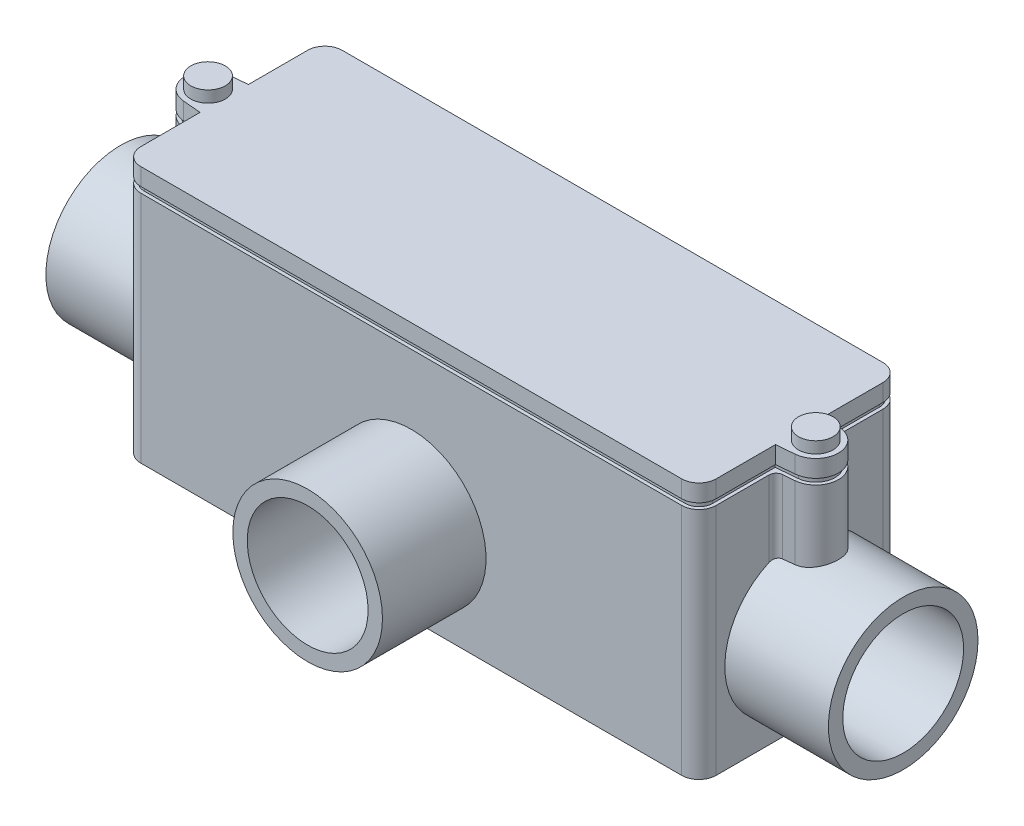
SolidWorks part; units mm, degrees
material "PVC Rigid"
ref_plane "Front" through (0, 0, 0) normal (0, 0, 1) x (1, 0, 0)
ref_plane "Top" through (0, 0, 0) normal (0, 1, 0) x (1, 0, 0)
ref_plane "Right" through (0, 0, 0) normal (1, 0, 0) x (0, 0, -1)
sketch "Sketch2" plane through (0, 0, 0) normal (0, 1, 0) x (1, 0, 0)
  line L0 (63.5, -22.225) -> (-63.5, 22.225) construction
  line L1 (-63.5, 22.225) -> (63.5, 22.225)
  line L2 (-63.5, 22.225) -> (-63.5, -22.225)
  line L3 (-63.5, -22.225) -> (63.5, -22.225)
  line L4 (63.5, 22.225) -> (63.5, -22.225)
  dimension "BoxLength" = 127
  dimension "BoxWidth" = 44.45
extrude "Base-Extrude" add sketch "Sketch2" along normal blind 51.6128
fillet "Fillet1" radius 3.81 4 edges at (-63.5, 25.8064, 22.225) (63.5, 25.8064, 22.225) (63.5, 25.8064, -22.225) (-63.5, 25.8064, -22.225)
shell "Shell1" thickness 3.556 removed face at (0, 51.6128, 0)
ref_plane "Plane1" through (0, -15, 0) normal (0, -1, 0) x (1, 0, 0)
sketch "Sketch1" plane through (63.5, 0, 0) normal (1, 0, 0) x (0, 0, -1)
  line L0 (0, 0) -> (0, 56.0378) construction
  line L2 (-18.415, 0) -> (18.415, 0) construction
  line L3 (-18.415, 0) -> (18.415, 0) construction
  circle A0 centre (0, 19.812) radius 16.51
  point P7 (0, 0)
  dimension "ConduitHubDia" = 33.02
  dimension "D2" = 3.302
extrude "ConduitBoss-Extrude1" add sketch "Sketch1" along normal blind 22.86
sketch "Sketch5" plane through (0, 51.6128, 0) normal (0, 1, 0) x (-1, 0, 0)
  line L0 (0, 0) -> (-73.6061, 0) construction
  line L1 (-63.5, -5.334) -> (-63.5, 5.334)
  line L2 (-63.5, 5.334) -> (-67.5078, 4.9807)
  line L3 (-63.5, -5.334) -> (-67.5078, -4.9807)
  line L4 (-63.5, 18.415) -> (-63.5, -18.415) construction
  line L5 (0, 0) -> (0, -39.7001) construction
  line L7 (63.5, 5.334) -> (67.5078, 4.9807)
  line L8 (63.5, -5.334) -> (67.5078, -4.9807)
  line L9 (63.5, -5.334) -> (63.5, 5.334)
  arc A0 (-67.5078, 4.9807) -> (-67.5078, -4.9807) centre (-67.0687, 0) ccw
  arc A1 (67.5078, 4.9807) -> (67.5078, -4.9807) centre (67.0687, 0) cw
  point P6 (-63.5, 0)
  dimension "D1" = 5
  dimension "D2" = 10.668
  dimension "L2-holeTOhole" = 134.1374
extrude "CoverScrewBoss-Extrude6" add sketch "Sketch5" against normal blind 20
sketch "Sketch18" plane through (0, 0, 22.225) normal (0, 0, 1) x (1, 0, 0)
  line L0 (0, 0) -> (0, 47.1321) construction
  line L1 (-59.69, 0) -> (59.69, 0) construction
  circle A0 centre (0, 19.812) radius 16.51
  dimension "BossOD" = 33.02
  dimension "BossOffsetoffBottom" = 3.302
extrude "SideConduitBoss-Extrude2" add sketch "Sketch18" along normal blind 22.86
sketch "Sketch10" plane through (86.36, 0, 0) normal (1, 0, 0) x (0, 0, -1)
  circle A0 centre (0, 19.812) radius 13.335
  circle A1 centre (0, 19.812) radius 16.51 construction
  dimension "ConduitSocketDia" = 26.67
extrude "ConduitSocket-Cut-Extrude4" cut sketch "Sketch10" against normal blind 19.8374
sketch "Sketch16" plane through (66.5226, 0, 0) normal (1, 0, 0) x (0, 1, 0)
  circle A0 centre (19.812, 0) radius 10.795
  circle A1 centre (19.812, 0) radius 16.51 construction
  dimension "ThruDIA" = 21.59
extrude "ThruDia-Cut-Extrude7" cut sketch "Sketch16" against normal up to surface (6.5786 mm away) up to face at (59.944, 27.5844, 0)
mirror "Mirror1" about plane through (0, 0, 0) normal (1, 0, 0) of "ConduitBoss-Extrude1", "ConduitSocket-Cut-Extrude4", "ThruDia-Cut-Extrude7"
sketch "Sketch19" plane through (0, 0, 45.085) normal (0, 0, 1) x (1, 0, 0)
  circle A0 centre (0, 19.812) radius 13.335
  circle A1 centre (0, 19.812) radius 16.51 construction
  dimension "CondSocketDia" = 26.67
extrude "Cut-Extrude1" cut sketch "Sketch19" against normal blind 19.8374
sketch "Sketch20" plane through (0, 0, 25.2476) normal (0, 0, 1) x (1, 0, 0)
  circle A0 centre (0, 19.812) radius 10.795
  circle A1 centre (0, 19.812) radius 13.335 construction
  dimension "ThruDIA" = 21.59
extrude "Cut-Extrude2" cut sketch "Sketch20" against normal up to surface (6.5786 mm away) up to face at (0, 27.5844, 18.669)
other "CPoint1" parameters "Diameter"=19.05, "StubLength"=0
ref_axis "Axis7" through (76.5226, 19.812, 0) along (-1, 0, 0)
other "CPoint2" parameters "Diameter"=19.05, "StubLength"=0
ref_axis "Axis8" through (-76.5226, 19.812, 0) along (1, 0, 0)
other "CPoint3" parameters "Diameter"=19.05, "StubLength"=0
ref_axis "Axis9" through (0, 19.812, 35.2476) along (0, 0, -1)
ref_point "Point1"
ref_point "Point2"
ref_point "Point3"
ref_plane "Plane2" through (0, 19.812, 0) normal (0, 1, 0) x (-1, 0, 0)
sketch "Sketch21" plane through (0, 19.812, 0) normal (0, 1, 0) x (-1, 0, 0)
  line L0 (66.5226, 0) -> (-66.5226, 0) construction
  line L1 (0, 25.2476) -> (0, 0) construction
other "RPoint1"
sketch "Sketch22" plane through (0, 51.6128, 0) normal (0, 1, 0) x (-1, 0, 0)
  line L10 (63.5, -18.415) -> (63.5, -5.334)
  line L11 (63.5, -5.334) -> (67.5078, -4.9807)
  line L12 (67.5078, 4.9807) -> (63.5, 5.334)
  line L13 (63.5, 5.334) -> (63.5, 18.415)
  line L14 (59.69, 22.225) -> (-59.69, 22.225)
  line L15 (-63.5, 18.415) -> (-63.5, 5.334)
  line L16 (-63.5, 5.334) -> (-67.5078, 4.9807)
  line L17 (-67.5078, -4.9807) -> (-63.5, -5.334)
  line L18 (-63.5, -5.334) -> (-63.5, -18.415)
  line L19 (-59.69, -22.225) -> (59.69, -22.225)
  line L20 (63.5, -18.415) -> (63.5, -5.334)
  line L21 (63.5, -5.334) -> (67.5078, -4.9807)
  line L22 (67.5078, 4.9807) -> (63.5, 5.334)
  line L23 (63.5, 5.334) -> (63.5, 18.415)
  line L24 (59.69, 22.225) -> (-59.69, 22.225)
  line L25 (-63.5, 18.415) -> (-63.5, 5.334)
  line L26 (-63.5, 5.334) -> (-67.5078, 4.9807)
  line L27 (-67.5078, -4.9807) -> (-63.5, -5.334)
  line L28 (-63.5, -5.334) -> (-63.5, -18.415)
  line L29 (-59.69, -22.225) -> (59.69, -22.225)
  arc A6 (67.5078, -4.9807) -> (67.5078, 4.9807) centre (67.0687, 0) ccw
  arc A7 (63.5, 18.415) -> (59.69, 22.225) centre (59.69, 18.415) ccw
  arc A8 (-59.69, 22.225) -> (-63.5, 18.415) centre (-59.69, 18.415) ccw
  arc A9 (-67.5078, 4.9807) -> (-67.5078, -4.9807) centre (-67.0687, 0) ccw
  arc A10 (-63.5, -18.415) -> (-59.69, -22.225) centre (-59.69, -18.415) ccw
  arc A11 (59.69, -22.225) -> (63.5, -18.415) centre (59.69, -18.415) ccw
  arc A12 (67.5078, -4.9807) -> (67.5078, 4.9807) centre (67.0687, 0) ccw
  arc A13 (63.5, 18.415) -> (59.69, 22.225) centre (59.69, 18.415) ccw
  arc A14 (-59.69, 22.225) -> (-63.5, 18.415) centre (-59.69, 18.415) ccw
  arc A15 (-67.5078, 4.9807) -> (-67.5078, -4.9807) centre (-67.0687, 0) ccw
  arc A16 (-63.5, -18.415) -> (-59.69, -22.225) centre (-59.69, -18.415) ccw
  arc A17 (59.69, -22.225) -> (63.5, -18.415) centre (59.69, -18.415) ccw
  dimension "D1" = 0
fillet "Fillet2" radius 1.524 4 edges at (63.5, 43.5247, 5.334) (63.5, 43.5247, -5.334) (-63.5, 43.5247, -5.334) (-63.5, 43.5247, 5.334)
sketch "Sketch23" plane through (0, 51.6128, 0) normal (0, 1, 0) x (-1, 0, 0)
  line L20 (62.738, 4.6362) -> (62.738, 18.415)
  line L21 (67.4409, 4.2216) -> (62.738, 4.6362)
  line L22 (62.738, -4.6362) -> (67.4409, -4.2216)
  line L23 (62.738, -18.415) -> (62.738, -4.6362)
  line L24 (-59.69, -21.463) -> (59.69, -21.463)
  line L25 (-62.738, -4.6362) -> (-62.738, -18.415)
  line L26 (-67.4409, -4.2216) -> (-62.738, -4.6362)
  line L27 (-62.738, 4.6362) -> (-67.4409, 4.2216)
  line L28 (-62.738, 18.415) -> (-62.738, 4.6362)
  line L29 (59.69, 21.463) -> (-59.69, 21.463)
  line L30 (62.738, 4.6362) -> (62.738, 18.415)
  line L31 (67.4409, 4.2216) -> (62.738, 4.6362)
  line L32 (62.738, -4.6362) -> (67.4409, -4.2216)
  line L33 (62.738, -18.415) -> (62.738, -4.6362)
  line L34 (-59.69, -21.463) -> (59.69, -21.463)
  line L35 (-62.738, -4.6362) -> (-62.738, -18.415)
  line L36 (-67.4409, -4.2216) -> (-62.738, -4.6362)
  line L37 (-62.738, 4.6362) -> (-67.4409, 4.2216)
  line L38 (-62.738, 18.415) -> (-62.738, 4.6362)
  line L39 (59.69, 21.463) -> (-59.69, 21.463)
  arc A12 (62.738, 18.415) -> (59.69, 21.463) centre (59.69, 18.415) ccw
  arc A13 (67.4409, -4.2216) -> (67.4409, 4.2216) centre (67.0687, 0) ccw
  arc A14 (59.69, -21.463) -> (62.738, -18.415) centre (59.69, -18.415) ccw
  arc A15 (-62.738, -18.415) -> (-59.69, -21.463) centre (-59.69, -18.415) ccw
  arc A16 (-67.4409, 4.2216) -> (-67.4409, -4.2216) centre (-67.0687, 0) ccw
  arc A17 (-59.69, 21.463) -> (-62.738, 18.415) centre (-59.69, 18.415) ccw
  arc A18 (62.738, 18.415) -> (59.69, 21.463) centre (59.69, 18.415) ccw
  arc A19 (67.4409, -4.2216) -> (67.4409, 4.2216) centre (67.0687, 0) ccw
  arc A20 (59.69, -21.463) -> (62.738, -18.415) centre (59.69, -18.415) ccw
  arc A21 (-62.738, -18.415) -> (-59.69, -21.463) centre (-59.69, -18.415) ccw
  arc A22 (-67.4409, 4.2216) -> (-67.4409, -4.2216) centre (-67.0687, 0) ccw
  arc A23 (-59.69, 21.463) -> (-62.738, 18.415) centre (-59.69, 18.415) ccw
  dimension "D1" = 0.762
extrude "Extrude2" add sketch "Sketch23" along normal blind 1.27
sketch "Sketch24" plane through (0, 52.8828, 0) normal (0, 1, 0) x (-1, 0, 0)
  line L0 (-63.5, -5.334) -> (-63.5, -18.415) construction
  line L1 (-67.5078, -4.9807) -> (-63.5, -5.334) construction
  line L2 (-63.5, 5.334) -> (-67.5078, 4.9807) construction
  line L3 (-63.5, 18.415) -> (-63.5, 5.334) construction
  line L4 (59.69, 22.225) -> (-59.69, 22.225) construction
  line L5 (63.5, 5.334) -> (63.5, 18.415) construction
  line L6 (67.5078, 4.9807) -> (63.5, 5.334) construction
  line L7 (63.5, -5.334) -> (67.5078, -4.9807) construction
  line L8 (63.5, -18.415) -> (63.5, -5.334) construction
  line L9 (-59.69, -22.225) -> (59.69, -22.225) construction
  line L10 (-63.5, -5.334) -> (-63.5, -18.415)
  line L11 (-67.5078, -4.9807) -> (-63.5, -5.334)
  line L12 (-63.5, 5.334) -> (-67.5078, 4.9807)
  line L13 (-63.5, 18.415) -> (-63.5, 5.334)
  line L14 (59.69, 22.225) -> (-59.69, 22.225)
  line L15 (63.5, 5.334) -> (63.5, 18.415)
  line L16 (67.5078, 4.9807) -> (63.5, 5.334)
  line L17 (63.5, -5.334) -> (67.5078, -4.9807)
  line L18 (63.5, -18.415) -> (63.5, -5.334)
  line L19 (-59.69, -22.225) -> (59.69, -22.225)
  arc A0 (-63.5, -18.415) -> (-59.69, -22.225) centre (-59.69, -18.415) ccw construction
  arc A1 (-67.5078, 4.9807) -> (-67.5078, -4.9807) centre (-67.0687, 0) ccw construction
  arc A2 (-59.69, 22.225) -> (-63.5, 18.415) centre (-59.69, 18.415) ccw construction
  arc A3 (63.5, 18.415) -> (59.69, 22.225) centre (59.69, 18.415) ccw construction
  arc A4 (67.5078, -4.9807) -> (67.5078, 4.9807) centre (67.0687, 0) ccw construction
  arc A5 (59.69, -22.225) -> (63.5, -18.415) centre (59.69, -18.415) ccw construction
  arc A6 (-63.5, -18.415) -> (-59.69, -22.225) centre (-59.69, -18.415) ccw
  arc A7 (-67.5078, 4.9807) -> (-67.5078, -4.9807) centre (-67.0687, 0) ccw
  arc A8 (-59.69, 22.225) -> (-63.5, 18.415) centre (-59.69, 18.415) ccw
  arc A9 (63.5, 18.415) -> (59.69, 22.225) centre (59.69, 18.415) ccw
  arc A10 (67.5078, -4.9807) -> (67.5078, 4.9807) centre (67.0687, 0) ccw
  arc A11 (59.69, -22.225) -> (63.5, -18.415) centre (59.69, -18.415) ccw
extrude "Extrude3" add sketch "Sketch24" along normal blind 3.81
sketch "Sketch25" plane through (0, 56.6928, 0) normal (0, 1, 0) x (-1, 0, 0)
  circle A0 centre (67.0687, 0) radius 3.81
  circle A1 centre (-67.0687, 0) radius 3.81
  arc A4 (67.5078, -4.9807) -> (67.5078, 4.9807) centre (67.0687, 0) ccw construction
  arc A5 (-67.5078, 4.9807) -> (-67.5078, -4.9807) centre (-67.0687, 0) ccw construction
  dimension "D1" = 7.62
  dimension "D2" = 7.62
extrude "Extrude4" add sketch "Sketch25" along normal blind 2.54
